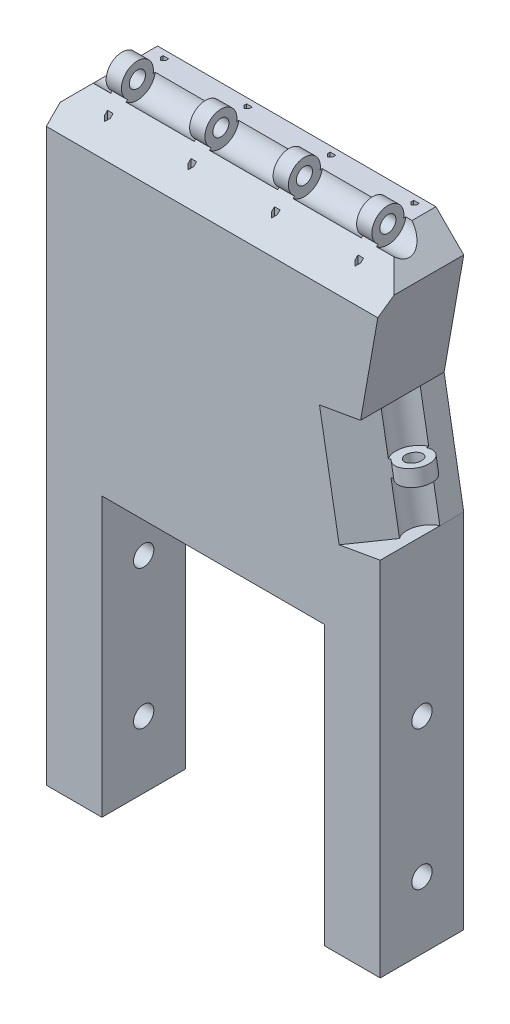
SolidWorks part; units mm, degrees
material "Custom Plastic"
ref_plane "Front Plane" through (0, 0, 0) normal (0, 0, 1) x (1, 0, 0)
ref_plane "Top Plane" through (0, 0, 0) normal (0, 1, 0) x (1, 0, 0)
ref_plane "Right Plane" through (0, 0, 0) normal (1, 0, 0) x (0, 0, -1)
sketch "Sketch1" plane through (0, 0, 0) normal (0, 0, 1) x (1, 0, 0)
  line L1 (-30, -30) -> (30, -30)
  line L2 (-30, -30) -> (-30, 30)
  line L3 (-30, 30) -> (30, 30)
  line L4 (30, -30) -> (30, 30)
  line L5 (-30, -30) -> (30, 30) construction
  line L6 (-30, 30) -> (30, -30) construction
  point P0 (0, 0)
  dimension "D1" = 60
  dimension "D2" = 60
extrude "Boss-Extrude1" add sketch "Sketch1" along normal mid plane 15
sketch "Sketch2" plane through (0, 0, 0) normal (0, 0, 1) x (1, 0, 0)
  line L0 (-30, 25) -> (-25, 30)
  line L1 (-30, 30) -> (-30, -30) construction
  line L2 (30, 30) -> (-30, 30) construction
  line L3 (-25, 30) -> (25, 30)
  line L4 (25, 30) -> (30, 25)
  line L5 (30, -30) -> (30, 30) construction
  line L10 (-30, -30) -> (30, -30) construction
  line L11 (14.5979, -30) -> (-15, -30)
  line L13 (-30, -15) -> (-30, 25)
  line L15 (-30, -15) -> (-30, -30)
  line L16 (-30, -30) -> (-15, -30)
  line L17 (14.5979, -30) -> (30, -30)
  line L18 (30, -30) -> (30, -15)
  line L19 (30, 25) -> (26.4735, 5)
  line L20 (26.4735, 5) -> (30, -15)
  dimension "D1" = 5
  dimension "D2" = 5
  dimension "D3" = 5
  dimension "D4" = 5
  dimension "D5" = 170
  dimension "D6" = 20
  dimension "D7" = 15
extrude "Cut-Extrude6" cut sketch "Sketch2" against normal through all both and the other way through all flip side to cut
ref_plane "Plane1" through (29.5, 0, 0) normal (1, 0, 0) x (0, 0, -1)
sketch "Sketch9" plane through (0, 0, 0) normal (1, 0, 0) x (0, 0, -1)
  line L0 (-7.5, 30) -> (0, 30)
  line L1 (7.5, 30) -> (-7.5, 30) construction
  line L7 (0, 30) -> (-7.5, 22.5)
  line L8 (-7.5, 5) -> (-7.5, 25) construction
  line L9 (-7.5, 22.5) -> (-7.5, 30)
  dimension "D1" = 45
  dimension "D2" = 7.5
extrude "Cut-Extrude7" cut sketch "Sketch9" against normal through all both and the other way through all
sketch "Sketch25" plane through (0, -30, 0) normal (0, -1, 0) x (1, 0, 0)
  line L0 (-30, 7.5) -> (30, 7.5) construction
  line L1 (-30, -7.5) -> (-20, -7.5)
  line L2 (-30, -7.5) -> (-30, 7.5)
  line L3 (-30, 7.5) -> (-20, 7.5)
  line L4 (-20, -7.5) -> (-20, 7.5)
  line L5 (-30, -7.5) -> (-20, 7.5) construction
  line L6 (-30, 7.5) -> (-20, -7.5) construction
  line L8 (0, -8.25) -> (0, 8.25) construction
  line L9 (30, 7.5) -> (20, 7.5)
  line L10 (20, -7.5) -> (20, 7.5)
  line L11 (30, -7.5) -> (20, -7.5)
  line L12 (30, -7.5) -> (30, 7.5)
  point P0 (-25, 0)
  dimension "D1" = 15
  dimension "D2" = 10
  dimension "D3" = 20
extrude "Boss-Extrude5" add sketch "Sketch25" along normal blind 50
sketch "Sketch26" plane through (-20, 0, 0) normal (1, 0, 0) x (0, 0, -1)
  line L5 (7.5, -80) -> (-7.5, -80) construction
  circle A0 centre (0, -68) radius 1.825
  circle A1 centre (0, -43) radius 1.825
  dimension "D1" = 3.65
  dimension "D2" = 3.65
  dimension "D3" = 12
  dimension "D4" = 25
extrude "Cut-Extrude22" cut sketch "Sketch26" against normal through all both and the other way through all
ref_plane "Plane4" through (-22.5, 0, 0) normal (-1, 0, 0) x (0, 0, 1)
sketch "Sketch28" plane through (-22.5, 0, 0) normal (-1, 0, 0) x (0, 0, 1)
  circle A0 centre (0, 30.5) radius 2.875
  dimension "D2" = 5.75
  dimension "D1" = 0.5
extrude "Boss-Extrude6" add sketch "Sketch28" along normal mid plane 2.75
pattern_linear "LPattern1" count 4 spacing 15 along (1, 0, 0) of "Boss-Extrude6"
sketch "Sketch29" plane through (-21.125, 0, 0) normal (1, 0, 0) x (0, 0, -1)
  circle A0 centre (0, 30.5) radius 3.25
  dimension "D1" = 6.5
extrude "Cut-Extrude23" cut sketch "Sketch29" along normal blind 12.25
mirror "Mirror1" about plane through (-22.5, 0, 0) normal (-1, 0, 0) of "Cut-Extrude23"
pattern_linear "LPattern2" count 4 spacing 15 along (1, 0, 0) of "Cut-Extrude23"
ref_plane "Plane5" through (1.7065, -9.678, 0) normal (-0.1736, 0.9848, 0) x (0.9848, 0.1736, 0)
sketch "Sketch31" plane through (1.7065, -9.678, 0) normal (-0.1736, 0.9848, 0) x (0.9848, 0.1736, 0)
  line L0 (26.9395, -7.5) -> (19.4395, -7.5)
  line L1 (19.4395, -7.5) -> (26.9395, 0)
  line L2 (26.9395, 0) -> (26.9395, -7.5)
  line L7 (26.9395, 7.5) -> (26.9395, -7.5) construction
  line L8 (26.9395, -7.5) -> (33.0172, -7.5) construction
  dimension "D1" = 45
  dimension "D2" = 7.5
extrude "Cut-Extrude25" cut sketch "Sketch31" against normal up to vertex (10.1543 mm away) and the other way up to vertex (10.1543 mm away) up to point (30, -15, 7.5) other way up to point (26.4735, 5, -7.5)
sketch "Sketch32" plane through (1.7065, -9.678, 0) normal (-0.1736, 0.9848, 0) x (0.9848, 0.1736, 0)
  circle A0 centre (27.4395, 0) radius 2.875
  dimension "D2" = 5.75
  dimension "D1" = 0.5
extrude "Boss-Extrude7" add sketch "Sketch32" along normal mid plane 2.75
sketch "Sketch33" plane through (1.9453, -11.0321, 0) normal (0.1736, -0.9848, 0) x (0.9848, 0.1736, 0)
  circle A0 centre (27.4395, 0) radius 3.25
  dimension "D1" = 6.5
extrude "Cut-Extrude26" cut sketch "Sketch33" along normal up to vertex (8.7793 mm away) up to point (30, -15, 0)
mirror "Mirror2" about plane through (1.7065, -9.678, 0) normal (-0.1736, 0.9848, 0) of "Cut-Extrude26"
sketch "Sketch34" plane through (1.9453, -11.0321, 0) normal (0.1736, -0.9848, 0) x (0.9848, 0.1736, 0)
  circle A0 centre (27.4395, 0) radius 1.45
  dimension "D1" = 2.9
extrude "Cut-Extrude27" cut sketch "Sketch34" against normal up to surface (2.75 mm away) up to face at (27.6908, -3.7, -0.316)
sketch "Sketch35" plane through (23.875, 0, 0) normal (1, 0, 0) x (0, 0, -1)
  circle A0 centre (0, 30.5) radius 1.45
  dimension "D1" = 2.9
extrude "Cut-Extrude28" cut sketch "Sketch35" against normal up to surface (47.75 mm away) up to face at (-23.875, 29.6881, -0.316)
sketch "Sketch36" plane through (0, -30, 0) normal (0, -1, 0) x (1, 0, 0)
  line L0 (0, 6.5) -> (-2, 4.5)
  line L1 (-2, 4.5) -> (-2, 2.5)
  line L2 (-2, 2.5) -> (2, 2.5)
  line L3 (2, 2.5) -> (2, 4.5)
  line L4 (2, 4.5) -> (0, 6.5)
  line L5 (-20, 7.5) -> (20, 7.5) construction
  point P8 (0, 7.5)
  dimension "D1" = 2
  dimension "D2" = 135
  dimension "D3" = 2
  dimension "D4" = 135
  dimension "D5" = 4
  dimension "D6" = 1
extrude "Cut-Extrude29" cut sketch "Sketch36" against normal up to surface (30 mm away) up to plane "Top Plane"
pattern_linear "LPattern3" count 2 spacing 9 along (0, 0, -1) of "Cut-Extrude29"
sketch "Sketch41" plane through (0, 30, 0) normal (0, 1, 0) x (1, 0, 0)
  line L0 (-23, 6.5) -> (-22, 6.5)
  line L1 (-22, 6.5) -> (-22, 6)
  line L2 (-22, 6) -> (-22.5, 5.5)
  line L3 (-22.5, 8.25) -> (-22.5, -8.25) construction
  line L4 (-22.5, 5.5) -> (-23, 6)
  line L5 (-23, 6) -> (-23, 6.5)
  line L6 (25, 7.5) -> (-25, 7.5) construction
  line L7 (-8, 6) -> (-8, 6.5)
  line L8 (-8, 6.5) -> (-7, 6.5)
  line L9 (-7, 6.5) -> (-7, 6)
  line L10 (-7, 6) -> (-7.5, 5.5)
  line L11 (-7.5, 5.5) -> (-8, 6)
  line L12 (7, 6) -> (7, 6.5)
  line L13 (7, 6.5) -> (8, 6.5)
  line L14 (8, 6.5) -> (8, 6)
  line L15 (8, 6) -> (7.5, 5.5)
  line L16 (7.5, 5.5) -> (7, 6)
  line L17 (22, 6) -> (22, 6.5)
  line L18 (22, 6.5) -> (23, 6.5)
  line L19 (23, 6.5) -> (23, 6)
  line L20 (23, 6) -> (22.5, 5.5)
  line L21 (22.5, 5.5) -> (22, 6)
  line L22 (-8, -4) -> (-8, -3.5)
  line L23 (-8, -3.5) -> (-7, -3.5)
  line L24 (-7, -3.5) -> (-7, -4)
  line L25 (-7, -4) -> (-7.5, -4.5)
  line L26 (-7.5, -4.5) -> (-8, -4)
  line L27 (7, -4) -> (7, -3.5)
  line L28 (7, -3.5) -> (8, -3.5)
  line L29 (8, -3.5) -> (8, -4)
  line L30 (8, -4) -> (7.5, -4.5)
  line L31 (7.5, -4.5) -> (7, -4)
  line L32 (22, -4) -> (22, -3.5)
  line L33 (22, -3.5) -> (23, -3.5)
  line L34 (23, -3.5) -> (23, -4)
  line L35 (23, -4) -> (22.5, -4.5)
  line L36 (22.5, -4.5) -> (22, -4)
  line L37 (-23, -4) -> (-23, -3.5)
  line L38 (-23, -3.5) -> (-22, -3.5)
  line L39 (-22, -3.5) -> (-22, -4)
  line L40 (-22, -4) -> (-22.5, -4.5)
  line L41 (-22.5, -4.5) -> (-23, -4)
  dimension "D1" = 0.5
  dimension "D2" = 0.5
  dimension "D3" = 135
  dimension "D4" = 1
  dimension "D5" = 1
  dimension "D8" = 9
  dimension "D6" = 4
  dimension "D7" = 2
extrude "Cut-Extrude32" cut sketch "Sketch41" against normal blind 10
ref_plane "Plane6" through (-11, 11, 0) normal (-0.7071, 0.7071, 0) x (0.7071, 0.7071, 0)
sketch "Sketch42" plane through (-11, 11, 0) normal (-0.7071, 0.7071, 0) x (0.7071, 0.7071, 0)
  line L0 (-0.9221, -4.5) -> (-1.4142, -4.0079)
  line L1 (-1.4142, -4.0079) -> (-1.4142, -3.5079)
  line L2 (-1.4142, -3.5079) -> (-0.4142, -3.4921)
  line L3 (-0.4142, -3.4921) -> (-0.4142, -3.9921)
  line L4 (-0.4142, -3.9921) -> (-0.9221, -4.5)
  line L5 (-5.3033, -7.5) -> (-77.7817, -7.5) construction
  line L10 (-1.4142, -4) -> (-1.4142, -3.5) construction
  point P2 (1.0708, -2.2706)
  point P6 (1.1097, -2.2658)
  point P7 (0.8424, -2.2511)
  point P11 (0, 0)
  point P13 (-1.7054, -4.4921)
  dimension "D1" = 135
  dimension "D2" = 135
  dimension "D3" = 1
  dimension "D4" = 0.5
  dimension "D5" = 0.5
  dimension "D6" = 90.902
  dimension "D7" = 3
extrude "Cut-Extrude34" cut sketch "Sketch42" against normal up to surface and the other way up to surface up to face at (2, -15, 3.5) other way up to face at (-22, 23.125, 3.75)
